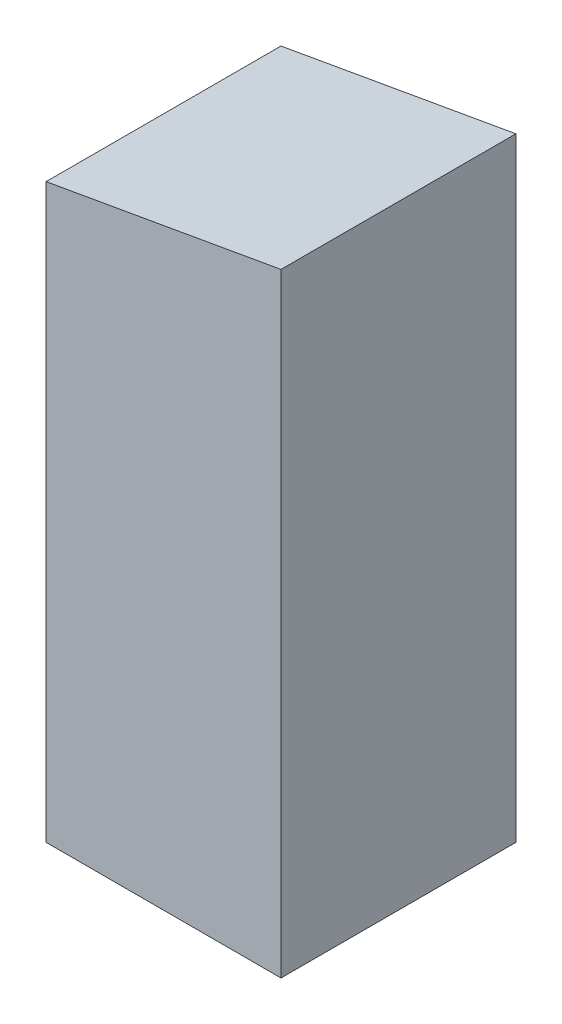
SolidWorks part; units mm, degrees
material "Oak"
ref_plane "Front Plane" through (0, 0, 0) normal (0, 0, 1) x (1, 0, 0)
ref_plane "Top Plane" through (0, 0, 0) normal (0, 1, 0) x (1, 0, 0)
ref_plane "Right Plane" through (0, 0, 0) normal (1, 0, 0) x (0, 0, -1)
sketch "Sketch1" plane through (0, 0, 0) normal (0, 1, 0) x (1, 0, 0)
  line L1 (-44.45, -44.45) -> (44.45, -44.45)
  line L2 (-44.45, -44.45) -> (-44.45, 44.45)
  line L3 (-44.45, 44.45) -> (44.45, 44.45)
  line L4 (44.45, -44.45) -> (44.45, 44.45)
  line L5 (-44.45, -44.45) -> (44.45, 44.45) construction
  line L6 (-44.45, 44.45) -> (44.45, -44.45) construction
  point P0 (0, 0)
  dimension "D1" = 88.9
  dimension "D2" = 88.9
extrude "Boss-Extrude1" add sketch "Sketch1" along normal blind 232.24
sketch "Sketch2" plane through (0, 0, 44.45) normal (0, 0, 1) x (1, 0, 0)
  line L0 (44.45, 232.24) -> (-44.45, 216.5645)
  line L1 (-44.45, 232.24) -> (-44.45, 0) construction
  line L2 (-44.45, 216.5645) -> (-44.45, 232.24)
  line L3 (-44.45, 232.24) -> (44.45, 232.24)
  dimension "D1" = 10
extrude "Cut-Extrude1" cut sketch "Sketch2" against normal blind 135
